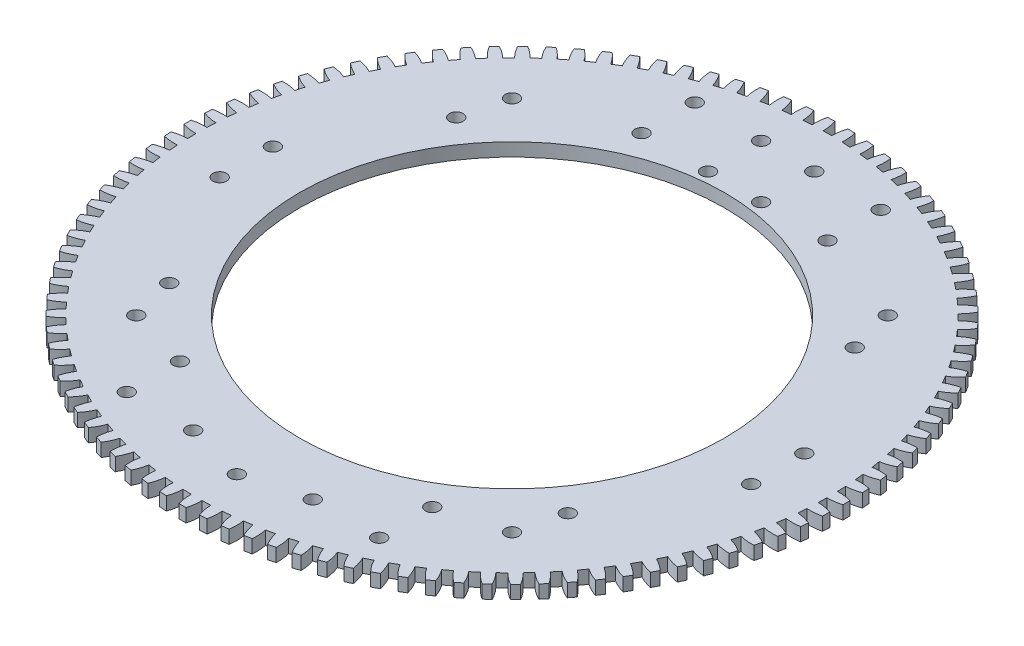
SolidWorks part; units mm, degrees
material "PC High Viscosity"
ref_plane "Front Plane" through (0, 0, 0) normal (0, 0, 1) x (1, 0, 0)
ref_plane "Top Plane" through (0, 0, 0) normal (0, 1, 0) x (1, 0, 0)
ref_plane "Right Plane" through (0, 0, 0) normal (1, 0, 0) x (0, 0, -1)
sketch "Sketch1" plane through (0, 0, 0) normal (0, 1, 0) x (1, 0, 0)
  circle A202 centre (0, 0) radius 152.4
  circle A203 centre (0, 0) radius 101.6
  dimension "D1" = 304.8
  dimension "D2" = 203.2
extrude "Boss-Extrude1" add sketch "Sketch1" along normal blind 6.35
sketch "Sketch2" [suppressed] plane through (0, 6.35, 0) normal (0, 1, 0) x (1, 0, 0)
  point P0 (0, 0)
sketch "Sketch3" [suppressed] plane through (0, 0, 0) normal (0, 0, 1) x (1, 0, 0)
  line L0 (0, -1000) -> (0, 49000) construction
sketch "Sketch8" plane through (0, 6.35, 0) normal (0, 1, 0) x (1, 0, 0)
  circle A0 centre (0, 0) radius 150.3251
  circle A1 centre (0, 0) radius 157.2724
extrude "Boss-Extrude2" add sketch "Sketch8" against normal blind 6.35
sketch "Sketch9" plane through (0, 6.35, 0) normal (0, 1, 0) x (1, 0, 0)
  circle A2 centre (0, 0) radius 157.4997
  point P3 (0, 0)
  point P5 (0, 0)
  dimension "D1" = 314.9994
extrude "Boss-Extrude3" add sketch "Sketch9" against normal blind 6.35
sketch "Sketch10" plane through (0, 6.35, 0) normal (0, 1, 0) x (1, 0, 0)
  circle A0 centre (0, 0) radius 154.4997
  circle A1 centre (0, 0) radius 157.4997
  circle A2 centre (0, 0) radius 150.7497
  dimension "D1" = 308.9994
  dimension "D2" = 314.9994
  dimension "D3" = 6.75
sketch "Sketch11" plane through (0, 6.35, 0) normal (0, 1, 0) x (1, 0, 0)
  line L0 (0, 0) -> (0, 178.9752) construction
  line L1 (0, 141.1196) -> (-2.3561, 154.4817) construction
  line L2 (0, 0) -> (-4.7116, 154.4278) construction
  line L3 (-2.3561, 154.4817) -> (-7.0661, 154.338) construction
  line L4 (-2.3561, 154.4817) -> (2.3561, 154.4817) construction
  arc A0 (-3.4509, 158.4621) -> (-2.0217, 150.7361) centre (-24.0388, 150.6585) cw
  arc A1 (3.4509, 158.4621) -> (2.0217, 150.7361) centre (24.0388, 150.6585) ccw
  circle A2 centre (0, 0) radius 150.7497 construction
  arc A3 (2.0217, 150.7361) -> (-2.0217, 150.7361) centre (0, 0) ccw
  arc A4 (3.4509, 158.4621) -> (-3.4509, 158.4621) centre (0, 0) ccw
  circle A5 centre (0, 0) radius 157.4997 construction
  circle A6 centre (0, 0) radius 154.4997 construction
  circle A7 centre (0, 0) radius 154.4997 construction
  dimension "D1" = 1
  dimension "D2" = 10
  dimension "D3" = 1.748
extrude "Cut-Extrude5" cut sketch "Sketch11" against normal blind 6.35
pattern_circular "CirPattern1" count 103 over 360 about axis through (0, 0, 0) along (0, 1, 0) of "Cut-Extrude5"
sketch "Sketch4" plane through (0, 6.35, 0) normal (0, 1, 0) x (1, 0, 0)
  line L0 (0, -1000) -> (0, 49000) construction
  line L1 (0, 106.3625) -> (-12.7, 106.3625) construction
  line L2 (-12.7, 106.3625) -> (-44.45, 106.3625) construction
  line L3 (0, 131.7625) -> (-12.7, 131.7625) construction
  line L4 (-12.7, 131.7625) -> (-44.45, 131.7625) construction
  circle A1 centre (-12.7, 106.3625) radius 3.2639
  circle A2 centre (-44.45, 106.3625) radius 3.2639
  circle A3 centre (-12.7, 131.7625) radius 3.2639
  circle A4 centre (-44.45, 131.7625) radius 3.2639
  circle A5 centre (12.7, 131.7625) radius 3.2639
  circle A6 centre (44.45, 131.7625) radius 3.2639
  circle A7 centre (44.45, 106.3625) radius 3.2639
  circle A8 centre (12.7, 106.3625) radius 3.2639
  point P1 (0, 106.3625)
  point P3 (0, 0)
  point P11 (0, 131.7625)
  dimension "D4" = 6.5278
  dimension "D5" = 6.5278
  dimension "D7" = 6.5278
  dimension "D8" = 6.5278
  dimension "D2" = 12.7
  dimension "D3" = 31.75
  dimension "D6" = 25.4
  dimension "D9" = 12.7
  dimension "D10" = 31.75
  dimension "D11" = 106.3625
extrude "Cut-Extrude1" cut sketch "Sketch4" against normal through all
sketch "Sketch5" plane through (0, 6.35, 0) normal (0, 1, 0) x (1, 0, 0)
  line L0 (0, 0) -> (0, -123.825) construction
  line L1 (0, -123.825) -> (-60.325, -123.825) construction
  line L2 (-60.325, -123.825) -> (-60.325, -98.425) construction
  line L3 (-60.325, -98.425) -> (-28.575, -98.425) construction
  line L4 (-28.575, -98.425) -> (-28.575, -123.825) construction
  circle A0 centre (-60.325, -123.825) radius 3.2639
  circle A1 centre (-60.325, -98.425) radius 3.2639
  circle A3 centre (-28.575, -123.825) radius 3.2639
  circle A4 centre (28.575, -123.825) radius 3.2639
  circle A5 centre (60.325, -123.825) radius 3.2639
  circle A6 centre (60.325, -98.425) radius 3.2639
  dimension "D2" = 6.5278
  dimension "D4" = 6.5278
  dimension "D8" = 6.5278
  dimension "D1" = 60.325
  dimension "D3" = 25.4
  dimension "D5" = 123.825
  dimension "D6" = 31.75
extrude "Cut-Extrude2" cut sketch "Sketch5" against normal blind 22.225
sketch "Sketch6" plane through (0, 6.35, 0) normal (0, 1, 0) x (1, 0, 0)
  line L0 (0, -1000) -> (0, 49000) construction
  line L1 (0, 0) -> (89.8026, -89.8026) construction
  circle A0 centre (89.8026, -89.8026) radius 3.2639
  circle A1 centre (-89.8026, -89.8026) radius 3.2639
  circle A2 centre (-89.8026, 89.8026) radius 3.2639
  circle A3 centre (89.8026, 89.8026) radius 3.2639
  dimension "D3" = 6.5278
  dimension "D1" = 45
  dimension "D2" = 127
  dimension "D4" = 4
extrude "Cut-Extrude3" cut sketch "Sketch6" against normal blind 6.35
sketch "Sketch7" plane through (0, 6.35, 0) normal (0, 1, 0) x (1, 0, 0)
  line L0 (0, 0) -> (-127, 0) construction
  line L1 (-127, 0) -> (-127, 12.7) construction
  line L2 (0, -1000) -> (0, 49000) construction
  circle A0 centre (-127, 12.7) radius 3.2639
  circle A1 centre (-127, -12.7) radius 3.2639
  circle A2 centre (127, -12.7) radius 3.2639
  circle A3 centre (127, 12.7) radius 3.2639
  dimension "D3" = 6.5278
  dimension "D1" = 127
  dimension "D2" = 12.7
extrude "Cut-Extrude4" cut sketch "Sketch7" against normal blind 6.35
sketch "Sketch12" plane through (0, 6.35, 0) normal (0, 1, 0) x (1, 0, 0)
  circle A0 centre (0, 0) radius 101.6
  dimension "D1" = 203.2
extrude "Cut-Extrude6" cut sketch "Sketch12" against normal through all
sketch "Sketch13" plane through (0, 6.35, 0) normal (0, 1, 0) x (1, 0, 0)
  line L0 (127, -12.7) -> (127, -68.58) construction
  line L1 (127, -68.58) -> (95.25, -68.58) construction
  line L2 (0, -1000) -> (0, 49000) construction
  line L3 (-1000, 0) -> (49000, 0) construction
  circle A0 centre (95.25, -68.58) radius 3.2639
  circle A1 centre (-95.25, -68.58) radius 3.2639
  circle A2 centre (-95.25, 68.58) radius 3.2639
  circle A3 centre (95.25, 68.58) radius 3.2639
  dimension "D3" = 6.5278
  dimension "D1" = 55.88
  dimension "D2" = 31.75
extrude "Cut-Extrude7" cut sketch "Sketch13" against normal blind 25.4
sketch "Sketch14" plane through (0, 0, 0) normal (0, -1, 0) x (1, 0, 0)
  line L0 (0, 0) -> (0, 121.92) construction
  line L1 (0, 121.92) -> (0, 128.27) construction
  line L2 (0, 131.5339) -> (0, 128.27) construction
  circle A0 centre (0, 131.5339) radius 3.2639
  dimension "D3" = 6.5278
  dimension "D1" = 121.92
  dimension "D2" = 6.35
extrude "Cut-Extrude8" cut sketch "Sketch14" against normal blind 6.35
